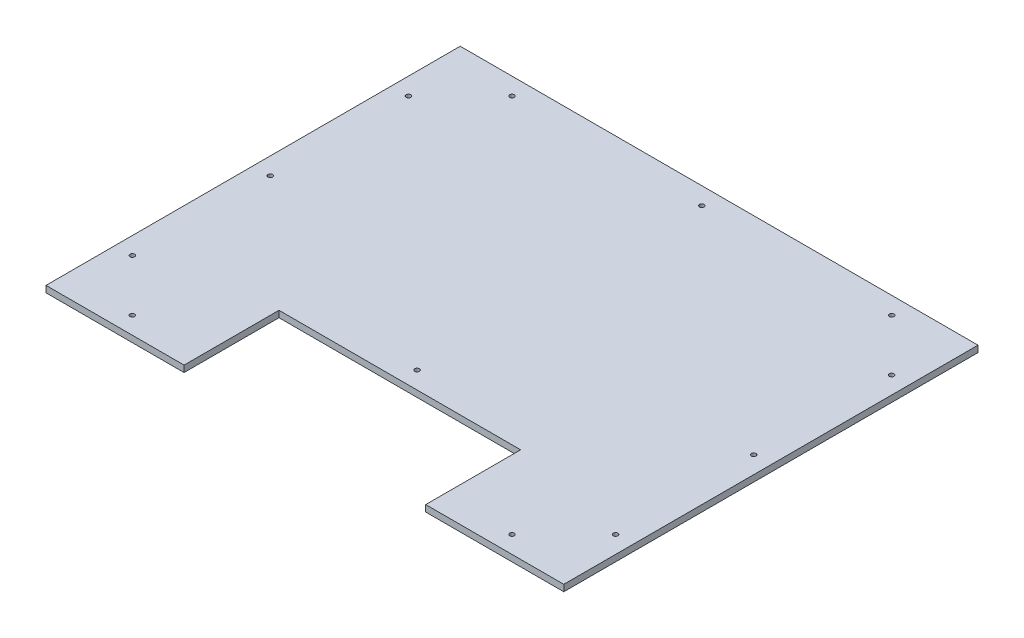
SolidWorks part; units mm, degrees
material "6061 Alloy"
ref_plane "Front Plane" through (0, 0, 0) normal (0, 0, 1) x (1, 0, 0)
ref_plane "Top Plane" through (0, 0, 0) normal (0, 1, 0) x (1, 0, 0)
ref_plane "Right Plane" through (0, 0, 0) normal (1, 0, 0) x (0, 0, -1)
sketch "Sketch1" plane through (0, 0, 0) normal (0, 1, 0) x (1, 0, 0)
  line L0 (0, 0) -> (0, -152.4) construction
  line L1 (-190.5, -152.4) -> (-88.9, -152.4)
  line L2 (-190.5, -152.4) -> (-190.5, 152.4)
  line L3 (-190.5, 152.4) -> (190.5, 152.4)
  line L4 (190.5, -152.4) -> (190.5, 152.4)
  line L5 (-190.5, -152.4) -> (190.5, 152.4) construction
  line L6 (-190.5, 152.4) -> (190.5, -152.4) construction
  line L8 (-88.9, -152.4) -> (-88.9, -82.55)
  line L9 (-88.9, -82.55) -> (88.9, -82.55)
  line L10 (88.9, -152.4) -> (88.9, -82.55)
  line L11 (88.9, -152.4) -> (190.5, -152.4)
  point P0 (0, 0)
  dimension "D1" = 304.8
  dimension "D2" = 381
  dimension "D3" = 69.85
  dimension "D4" = 177.8
extrude "Boss-Extrude1" add sketch "Sketch1" along normal blind 4.7625
sketch "Sketch2" plane through (0, 4.7625, 0) normal (0, 1, 0) x (1, 0, 0)
  line L0 (-177.8, 152.4) -> (-177.8, -152.4) construction
  line L1 (190.5, 152.4) -> (-190.5, 152.4) construction
  line L2 (-190.5, -152.4) -> (-88.9, -152.4) construction
  line L3 (-190.5, -139.7) -> (190.5, -139.7) construction
  line L4 (-190.5, 152.4) -> (-190.5, -152.4) construction
  line L5 (190.5, -152.4) -> (190.5, 152.4) construction
  line L6 (-190.5, 139.7) -> (190.5, 139.7) construction
  line L7 (177.8, 152.4) -> (177.8, -152.4) construction
  line L8 (-101.6, -152.4) -> (-101.6, -69.85) construction
  line L9 (-190.5, -152.4) -> (-88.9, -152.4) construction
  line L10 (-101.6, -69.85) -> (101.6, -69.85) construction
  line L11 (101.6, -69.85) -> (101.6, -152.4) construction
  line L12 (88.9, -152.4) -> (190.5, -152.4) construction
  line L13 (-88.9, -152.4) -> (-88.9, -82.55) construction
  line L14 (88.9, -82.55) -> (88.9, -152.4) construction
  line L15 (-88.9, -82.55) -> (88.9, -82.55) construction
  point P16 (-177.8, 0)
  point P18 (177.8, 0)
  point P19 (0, 139.7)
  point P20 (-177.8, 101.6)
  point P21 (-177.8, -101.6)
  point P22 (-139.7, 139.7)
  point P23 (-139.7, -139.7)
  point P24 (139.7, 139.7)
  point P25 (139.7, -139.7)
  point P26 (177.8, 101.6)
  point P27 (177.8, -101.6)
  point P38 (-88.9, -117.475)
  point P43 (0, -69.85)
  dimension "D1" = 12.7
  dimension "D2" = 12.7
  dimension "D3" = 12.7
  dimension "D4" = 12.7
  dimension "D5" = 50.8
  dimension "D6" = 50.8
  dimension "D7" = 50.8
  dimension "D8" = 50.8
  dimension "D9" = 12.7
  dimension "D10" = 12.7
  dimension "D11" = 12.7
hole_wizard "M3 Clearance Hole1" positions "3DSketch1" profile "Sketch3" hole size "M3" standard "ANSI Metric" end condition through all
sketch3d "3DSketch1"
  point P0 (-177.8, 4.7625, 101.6)
  point P3 (-177.8, 4.7625, 0)
  point P10 (-177.8, 4.7625, -101.6)
  point P13 (-139.7, 4.7625, -139.7)
  point P16 (0, 4.7625, -139.7)
  point P19 (139.7, 4.7625, -139.7)
  point P22 (177.8, 4.7625, -101.6)
  point P25 (177.8, 4.7625, 0)
  point P28 (177.8, 4.7625, 101.6)
  point P31 (139.7, 4.7625, 139.7)
  point P37 (-139.7, 4.7625, 139.7)
  point P43 (0, 4.7625, 69.85)
sketch "Sketch3" plane through (-177.8, 4.7625, 101.6) normal (1, 0, 0) x (0, 0, 1)
  line L0 (0, 0) -> (0, 4.7625)
  line L1 (0, 4.7625) -> (1.7, 4.7625)
  line L2 (1.7, 4.7625) -> (1.7, 0)
  line L5 (1.7, 0) -> (0, 0)
  line L11 (0, -6.35) -> (0, 107.95) construction
  dimension "Thru Hole Dia." = 3.4
  dimension "Thru Hole Depth" = 4.7625
equation "\"D3@Sketch2\"=\"D1@Sketch2\""
equation "\"D4@Sketch2\"=\"D2@Sketch2\""
equation "\"D6@Sketch2\"=\"D5@Sketch2\""
equation "\"D7@Sketch2\"=\"D5@Sketch2\""
equation "\"D8@Sketch2\"=\"D5@Sketch2\""
equation "\"D9@Sketch2\"=\"D1@Sketch2\""
equation "\"D10@Sketch2\"=\"D1@Sketch2\""
equation "\"D11@Sketch2\"=\"D1@Sketch2\""
equation "\"D2@Sketch2\"=\"D1@Sketch2\""
